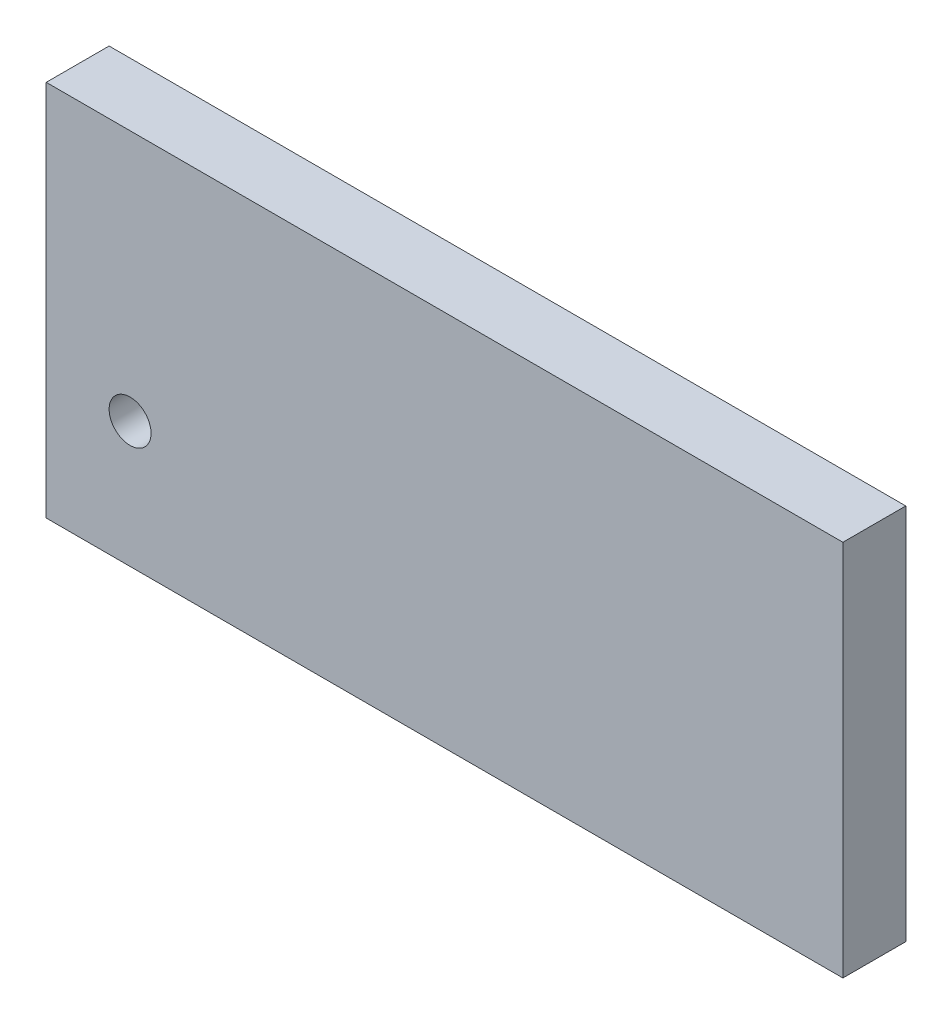
SolidWorks part; units mm, degrees
material "Pine"
ref_plane "Front Plane" through (0, 0, 0) normal (0, 0, 1) x (1, 0, 0)
ref_plane "Top Plane" through (0, 0, 0) normal (0, 1, 0) x (1, 0, 0)
ref_plane "Right Plane" through (0, 0, 0) normal (1, 0, 0) x (0, 0, -1)
sketch "Sketch2" plane through (0, 0, 0) normal (0, 0, 1) x (1, 0, 0)
  line L0 (251.8363, 27.1947) -> (493.1363, 27.1947)
  line L1 (251.8363, 141.4947) -> (493.1363, 141.4947)
  line L2 (251.8363, 141.4947) -> (251.8363, 27.1947)
  line L4 (493.1363, 141.4947) -> (493.1363, 27.1947)
  line L5 (251.8363, 141.4947) -> (467.7363, 141.4947) construction
  line L6 (251.8363, 27.1947) -> (467.7363, 27.1947) construction
  circle A0 centre (277.2363, 65.2947) radius 6.35
extrude "Boss-Extrude1" add sketch "Sketch2" along normal blind 19.05
